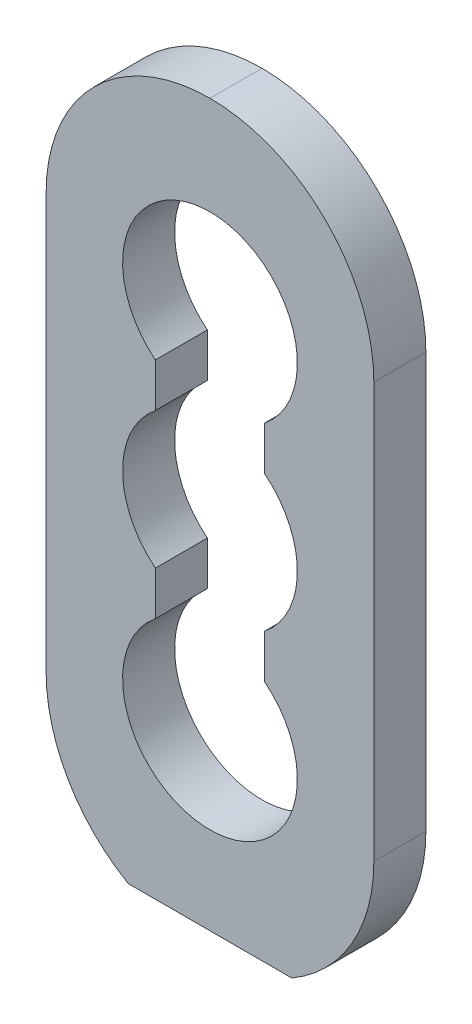
SolidWorks part; units mm, degrees
ref_plane "Alzado" through (0, 0, 0) normal (0, 0, 1) x (1, 0, 0)
ref_plane "Planta" through (0, 0, 0) normal (0, 1, 0) x (1, 0, 0)
ref_plane "Vista lateral" through (0, 0, 0) normal (1, 0, 0) x (0, 0, -1)
sketch "Croquis1" plane through (0, 0, 0) normal (0, 0, 1) x (1, 0, 0)
  line L0 (0, -14) -> (0, 14) construction
  line L1 (-15, 34) -> (15, 34)
  line L2 (-15, 34) -> (-15, -34)
  line L3 (-15, -34) -> (15, -34)
  line L4 (15, 34) -> (15, -34)
  line L33 (0, 14) -> (0, -14) construction
  line L34 (5, 14) -> (5, -14)
  line L35 (-5, 14) -> (-5, -14)
  arc A28 (5, 14) -> (-5, 14) centre (0, 14) ccw
  arc A29 (-5, -14) -> (5, -14) centre (0, -14) ccw
  point P4 (-15, 0)
  point P5 (0, 34)
  point P8 (0, 0)
  dimension "D5" = 28
  dimension "D2" = 5
  dimension "D1" = 30
  dimension "D3" = 20
  dimension "D4" = 20
  dimension "D8" = 15
extrude "Saliente-Extruir1" add sketch "Croquis1" along normal blind 4.7625
fillet "Redondeo1" radius 15 4 edges at (15, -34, 2.3813) (-15, -34, 2.3813) (-15, 34, 2.3813) (15, 34, 2.3813)
sketch "Croquis2" plane through (0, 0, 4.7625) normal (0, 0, 1) x (1, 0, 0)
  circle A0 centre (0, 17) radius 8
  circle A13 centre (0, 0.5) radius 8
  circle A14 centre (0, -16) radius 8
  dimension "D1" = 16
  dimension "D2" = 17
  dimension "D3" = 3
extrude "Cortar-Extruir1" cut sketch "Croquis2" against normal blind 10
sketch "Croquis3" plane through (0, 0, 4.7625) normal (0, 0, 1) x (1, 0, 0)
  line L0 (0, -34) -> (21.3041, -34) construction
  line L1 (-15.644, -32) -> (15.7609, -32)
  line L2 (-15.644, -32) -> (-15.644, -39.1979)
  line L3 (-15.644, -39.1979) -> (15.7609, -39.1979)
  line L4 (15.7609, -32) -> (15.7609, -39.1979)
  dimension "D1" = 2
extrude "Cortar-Extruir2" cut sketch "Croquis3" against normal blind 10
